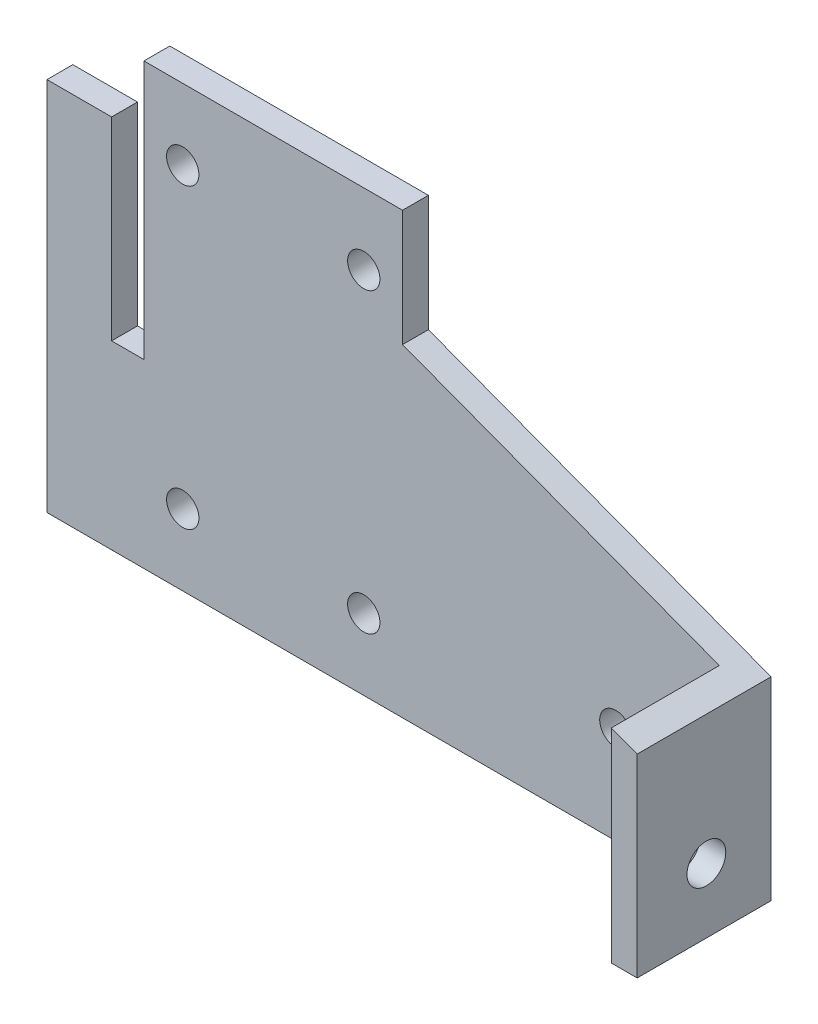
SolidWorks part; units mm, degrees
ref_plane "Спереди" through (0, 0, 0) normal (0, 0, 1) x (1, 0, 0)
ref_plane "Сверху" through (0, 0, 0) normal (0, 1, 0) x (1, 0, 0)
ref_plane "Справа" through (0, 0, 0) normal (1, 0, 0) x (0, 0, -1)
sketch "Эскиз1" plane through (0, 0, 0) normal (0, 0, 1) x (1, 0, 0)
  line L0 (35, 68) -> (35, 0) construction
  line L1 (0, 0) -> (108, 0)
  line L2 (0, 0) -> (0, 68)
  line L3 (0, 68) -> (55, 68)
  line L4 (108, 0) -> (108, 30)
  line L5 (21, 68) -> (21, 0) construction
  line L6 (55, 68) -> (55, 50)
  line L8 (49, 68) -> (49, 0) construction
  line L10 (108, 30) -> (55, 50)
  circle A0 centre (21, 57) radius 2.5
  circle A1 centre (49, 57) radius 2.5
  circle A2 centre (21, 11) radius 2.5
  circle A3 centre (49, 11) radius 2.5
  circle A4 centre (88, 15) radius 2.5
  dimension "D8" = 5
  dimension "D9" = 5
  dimension "D10" = 5
  dimension "D11" = 5
  dimension "D18" = 5
  dimension "D1" = 108
  dimension "D2" = 68
  dimension "D3" = 55
  dimension "D4" = 30
  dimension "D5" = 35
  dimension "D6" = 14
  dimension "D7" = 14
  dimension "D12" = 46
  dimension "D13" = 46
  dimension "D14" = 11
  dimension "D15" = 11
  dimension "D16" = 20
  dimension "D17" = 15
  dimension "D19" = 20
extrude "Бобышка-Вытянуть1" add sketch "Эскиз1" along normal blind 4
sketch "Эскиз2" plane through (0, 0, 4) normal (0, 0, 1) x (1, 0, 0)
  line L1 (108, 0) -> (104, 0)
  line L2 (0, 0) -> (108, 0) construction
  line L3 (104, 0) -> (104, 31.5094)
  line L4 (108, 30) -> (55, 50) construction
  line L5 (104, 31.5094) -> (108, 30)
  line L6 (108, 30) -> (108, 0)
  dimension "D1" = 4
extrude "Бобышка-Вытянуть2" add sketch "Эскиз2" along normal blind 16.7
sketch "Эскиз3" plane through (108, 0, 0) normal (1, 0, 0) x (0, 0, -1)
  line L4 (0, 0) -> (0, 30) construction
  line L5 (-20.7, 0) -> (0, 0) construction
  circle A1 centre (-10, 10) radius 3
  dimension "D2" = 10
  dimension "D3" = 6
  dimension "D1" = 10
extrude "Вырез-Вытянуть1" cut sketch "Эскиз3" against normal blind 10
sketch "Эскиз4" plane through (0, 0, 4) normal (0, 0, 1) x (1, 0, 0)
  line L1 (0, 68) -> (15, 68)
  line L2 (0, 68) -> (0, 58)
  line L3 (0, 58) -> (10, 58)
  line L4 (15, 68) -> (15, 58)
  line L6 (15, 58) -> (15, 28)
  line L7 (15, 28) -> (10, 28)
  line L8 (10, 58) -> (10, 28)
  dimension "D1" = 15
  dimension "D2" = 10
  dimension "D3" = 40
  dimension "D4" = 5
extrude "Вырез-Вытянуть2" cut sketch "Эскиз4" against normal blind 10
